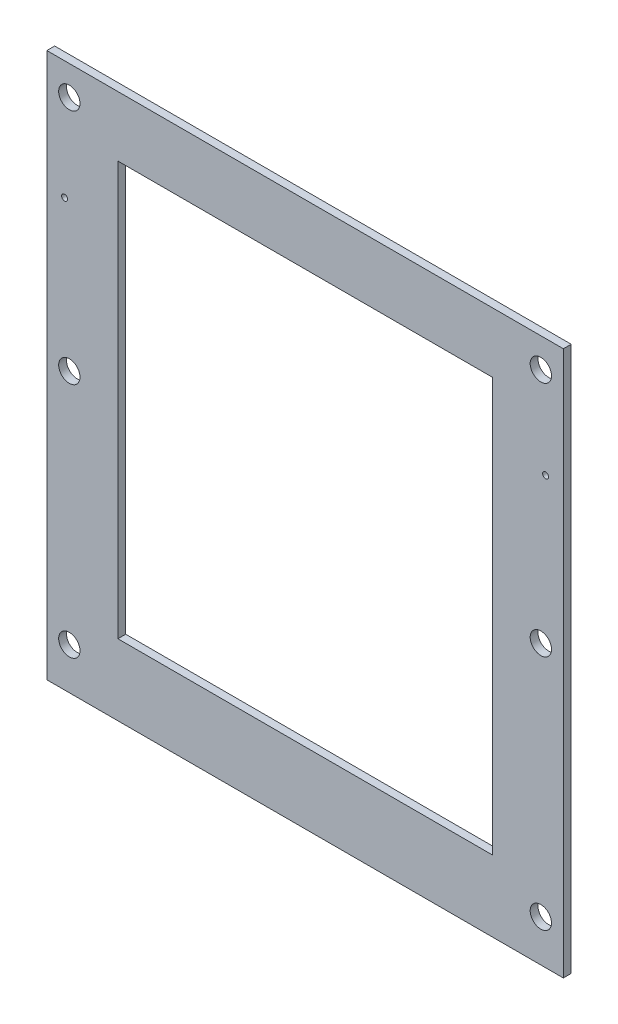
SolidWorks part; units mm, degrees
ref_plane "Front Plane" through (0, 0, 0) normal (0, 0, 1) x (1, 0, 0)
ref_plane "Top Plane" through (0, 0, 0) normal (0, 1, 0) x (1, 0, 0)
ref_plane "Right Plane" through (0, 0, 0) normal (1, 0, 0) x (0, 0, -1)
sketch "Sketch1" plane through (0, 0, 0) normal (0, 0, 1) x (1, 0, 0)
  line L0 (81.8848, 109.8822) -> (81.8848, -120.1178)
  line L2 (81.8848, -120.1178) -> (-136.1152, -120.1178)
  line L3 (-136.1152, 109.8822) -> (-136.1152, -120.1178)
  line L4 (-106.1152, 84.4822) -> (-106.1152, -90.1178)
  line L5 (51.8848, -90.1178) -> (-106.1152, -90.1178)
  line L6 (51.8848, 84.4822) -> (51.8848, -90.1178)
  line L8 (81.8848, 159.8822) -> (81.8848, -120.1178) construction
  line L9 (-106.1152, 109.8822) -> (51.8848, 109.8822)
  line L10 (-106.1152, 129.8822) -> (-106.1152, -90.1178) construction
  line L11 (51.8848, 129.8822) -> (-106.1152, 129.8822) construction
  line L12 (51.8848, 129.8822) -> (51.8848, -90.1178) construction
  line L14 (-136.1152, 159.8822) -> (-136.1152, -120.1178) construction
  line L15 (81.8848, 159.8822) -> (-136.1152, 159.8822) construction
  line L17 (-106.1152, 84.4822) -> (51.8848, 84.4822)
  line L18 (51.8848, 109.8822) -> (81.8848, 109.8822)
  line L19 (-106.1152, 109.8822) -> (-136.1152, 109.8822)
  circle A2 centre (-126.6152, 97.4822) radius 4.5
  circle A3 centre (-126.6152, -2.5178) radius 4.5
  circle A4 centre (-126.6152, -102.5178) radius 4.5
  circle A5 centre (72.3848, 97.4822) radius 4.5
  circle A6 centre (72.3848, -2.5178) radius 4.5
  circle A7 centre (72.3848, -102.5178) radius 4.5
  circle A8 centre (-128.6152, 59.8822) radius 1.25
  circle A9 centre (74.3848, 59.8822) radius 1.25
  dimension "D7" = 9.5
  dimension "D10" = 9.5
  dimension "D11" = 30
  dimension "D12" = 7.5
  dimension "D13" = 7.5
  dimension "D2" = 218
  dimension "D9" = 3
extrude "Boss-Extrude1" add sketch "Sketch1" along normal blind 3.302
